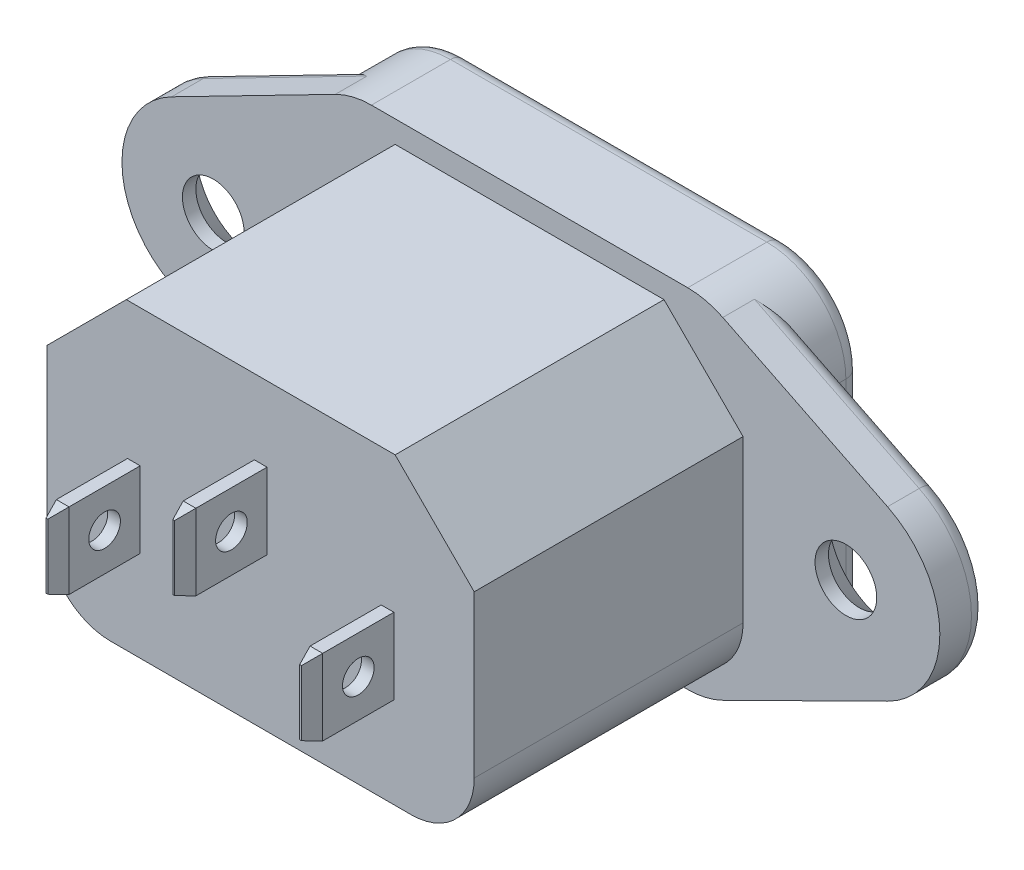
SolidWorks part; units mm, degrees
ref_plane "Front Plane" through (0, 0, 0) normal (0, 0, 1) x (1, 0, 0)
ref_plane "Top Plane" through (0, 0, 0) normal (0, 1, 0) x (1, 0, 0)
ref_plane "Right Plane" through (0, 0, 0) normal (1, 0, 0) x (0, 0, -1)
sketch "Sketch1" plane through (0, 0, 0) normal (0, 0, 1) x (1, 0, 0)
  line L0 (0, 14.2) -> (-5, 19.2)
  line L1 (-4, 0) -> (-23, 0)
  line L2 (0, 4) -> (0, 14.2)
  line L3 (-5, 19.2) -> (-22, 19.2)
  line L4 (-27, 4) -> (-27, 14.2)
  line L5 (-27, 14.2) -> (-22, 19.2)
  arc A0 (-4, 0) -> (0, 4) centre (-4, 4) ccw
  arc A1 (-27, 4) -> (-23, 0) centre (-23, 4) ccw
  point P1 (-27, 19.2)
  point P2 (0, 19.2)
  point P7 (0, 0)
  dimension "D3" = 4
  dimension "D4" = 4
  dimension "D1" = 19.2
  dimension "D2" = 27
extrude "Boss-Extrude1" add sketch "Sketch1" along normal blind 17
sketch "Sketch7" plane through (0, 0, 0) normal (0, 0, 1) x (1, 0, 0)
  line L0 (-13.5, 19.2) -> (-13.5, 0) construction
  line L1 (1.5, -1.4) -> (-28.5, -1.4)
  line L2 (1.5, -1.4) -> (1.5, 20.6)
  line L3 (1.5, 20.6) -> (-28.5, 20.6)
  line L4 (-28.5, -1.4) -> (-28.5, 20.6)
  line L5 (-5, 19.2) -> (-22, 19.2) construction
  line L6 (-23, 0) -> (-4, 0) construction
  line L7 (0, 9.6) -> (-27, 9.6) construction
  line L8 (0, 4) -> (0, 14.2) construction
  line L9 (-27, 14.2) -> (-27, 4) construction
  dimension "D1" = 22
  dimension "D2" = 30
extrude "Boss-Extrude5" add sketch "Sketch7" against normal blind 6
fillet "Fillet13" radius 5 4 edges at (1.5, -1.4, -3) (-28.5, -1.4, -3) (-28.5, 20.6, -3) (1.5, 20.6, -3)
sketch "Sketch8" plane through (0, 0, 0) normal (0, 0, 1) x (1, 0, 0)
  line L0 (-13.5, 31.1212) -> (-13.5, -11.3132) construction
  line L1 (-6.5, 17.6) -> (-20.5, 17.6)
  line L2 (-1.5, 12.6) -> (-1.5, 3.6)
  line L3 (-3.5, 1.6) -> (-23.5, 1.6)
  line L4 (-25.5, 12.6) -> (-25.5, 3.6)
  line L5 (-20.5, 17.6) -> (-25.5, 12.6)
  line L7 (20.2859, 9.6) -> (-48.0141, 9.6) construction
  line L8 (1.5, 3.6) -> (1.5, 15.6) construction
  line L9 (-28.5, 15.6) -> (-28.5, 3.6) construction
  line L10 (-5, 19.2) -> (-22, 19.2) construction
  line L11 (-23, 0) -> (-4, 0) construction
  line L12 (-6.5, 17.6) -> (-1.5, 12.6)
  arc A0 (-3.5, 1.6) -> (-1.5, 3.6) centre (-3.5, 3.6) ccw
  arc A1 (-25.5, 3.6) -> (-23.5, 1.6) centre (-23.5, 3.6) ccw
  point P0 (-1.5, 17.6)
  point P3 (-25.5, 17.6)
  point P20 (-25.5, 1.6)
  dimension "D3" = 2
  dimension "D4" = 2
  dimension "D1" = 24
  dimension "D2" = 16
  dimension "D5" = 5
  dimension "D6" = 5
extrude "Cut-Extrude1" cut sketch "Sketch8" along normal blind 16 and the other way blind 6
sketch "Sketch9" plane through (0, 0, 0) normal (0, 0, 1) x (1, 0, 0)
  line L0 (-13.5, 32.7328) -> (-13.5, -17.166) construction
  line L1 (-36.1355, 4.463) -> (-25.7824, -0.8487)
  line L2 (-36.1355, 14.737) -> (-25.7824, 20.0487)
  line L3 (50.8382, 9.6) -> (-68.6144, 9.6) construction
  line L4 (-3.5, 20.6) -> (-23.5, 20.6) construction
  line L5 (9.1356, 14.9256) -> (-1.2823, 20.0813)
  line L6 (9.1356, 4.2744) -> (-1.2823, -0.8813)
  line L7 (-23.5, -1.4) -> (-3.5, -1.4) construction
  line L8 (-1.2823, 20.0813) -> (-1.2823, -0.8813)
  line L9 (-1.2823, -0.8813) -> (-1.5852, -0.8164)
  line L10 (-25.7824, 20.0487) -> (-25.7824, -0.8487)
  line L11 (1.5, 3.6) -> (1.5, 15.6) construction
  line L12 (-28.5, 15.6) -> (-28.5, 3.6) construction
  arc A0 (9.1356, 4.2744) -> (9.1356, 14.9256) centre (6.5, 9.6) ccw
  arc A1 (1.5, 15.6) -> (-3.5, 20.6) centre (-3.5, 15.6) ccw construction
  arc A2 (-3.5, -1.4) -> (1.5, 3.6) centre (-3.5, 3.6) ccw construction
  arc A3 (-36.1355, 14.737) -> (-36.1355, 4.463) centre (-33.5, 9.6) ccw
  arc A4 (-28.5, 3.6) -> (-23.5, -1.4) centre (-23.5, 3.6) ccw construction
  arc A5 (-23.5, 20.6) -> (-28.5, 15.6) centre (-23.5, 15.6) ccw construction
  point P0 (6.5, 9.6)
  point P1 (-33.5, 9.6)
  dimension "D1" = 40
extrude "Boss-Extrude6" add sketch "Sketch9" against normal blind 3 contours L6 A0 L5 L8 | L2 A3 L1 L10
hole_wizard "CSK for M3.5 Flat Head Machine Screw1" positions "Sketch11" profile "Sketch10" countersink size "M3.5" standard "ANSI Metric" end condition up to next
sketch "Sketch11" plane through (0, 0, -3) normal (0, 0, -1) x (-1, 0, 0)
  line L0 (13.5, 27.5168) -> (13.5, -20.2429) construction
  line L1 (-16.2874, 9.6) -> (52.2441, 9.6) construction
  line L2 (3.5, 20.6) -> (23.5, 20.6) construction
  line L3 (23.5, -1.4) -> (3.5, -1.4) construction
  line L4 (28.5, 15.6) -> (28.5, 3.6) construction
  line L5 (-1.5, 15.6) -> (-1.5, 3.6) construction
  point P0 (-6.5, 9.6)
  point P2 (33.5, 9.6)
  dimension "D1" = 40
sketch "Sketch10" plane through (6.5, 9.6, -3) normal (1, 0, 0) x (0, 1, 0)
  line L0 (0, 0) -> (0, 3)
  line L1 (0, 3) -> (1.95, 3)
  line L2 (1.95, 3) -> (1.95, 2.15)
  line L3 (1.95, 2.15) -> (4.1, 0)
  line L5 (4.1, 0) -> (0, 0)
  line L6 (-1.95, 2.15) -> (-4.1, 0) construction
  line L11 (0, -6.35) -> (0, 107.95) construction
  dimension "Thru Hole Dia." = 3.9
  dimension "Thru Hole Depth" = 3
  dimension "Near C'Sink Dia." = 8.2
  dimension "Near C'Sink Angle" = 90
sketch "Sketch12" plane through (0, 0, 16) normal (0, 0, -1) x (-1, 0, 0)
  line L0 (1.5, 5.6) -> (25.5, 5.6) construction
  line L1 (4.21, 10.68) -> (6.75, 10.68)
  line L2 (4.21, 10.68) -> (4.21, 5.6)
  line L3 (4.21, 5.6) -> (6.75, 5.6)
  line L4 (6.75, 10.68) -> (6.75, 5.6)
  line L5 (20.25, 10.68) -> (22.79, 10.68)
  line L6 (20.25, 10.68) -> (20.25, 5.6)
  line L7 (20.25, 5.6) -> (22.79, 5.6)
  line L8 (22.79, 10.68) -> (22.79, 5.6)
  line L9 (12.23, 14.6159) -> (14.77, 14.6159)
  line L10 (12.23, 14.6159) -> (12.23, 9.5359)
  line L11 (12.23, 9.5359) -> (14.77, 9.5359)
  line L12 (14.77, 14.6159) -> (14.77, 9.5359)
  line L13 (1.5, 3.6) -> (1.5, 12.6) construction
  line L14 (25.5, 12.6) -> (25.5, 3.6) construction
  line L15 (13.5, 17.6) -> (13.5, 1.6) construction
  line L16 (6.5, 17.6) -> (20.5, 17.6) construction
  line L17 (23.5, 1.6) -> (3.5, 1.6) construction
  line L18 (23.5, -1.4) -> (3.5, -1.4) construction
  dimension "D1" = 2.54
  dimension "D2" = 5.08
  dimension "D3" = 13.5
  dimension "D4" = 7
  dimension "D5" = 10.9359
extrude "Boss-Extrude7" add sketch "Sketch12" along normal blind 15 and the other way blind 5.5
sketch "Sketch13" plane through (0, 0, 1) normal (0, 0, -1) x (-1, 0, 0)
  line L0 (6.75, 10.68) -> (4.21, 10.68) construction
  line L1 (4.21, 10.68) -> (6.75, 10.68)
  line L2 (4.21, 10.68) -> (4.21, 5.6)
  line L3 (4.21, 5.6) -> (6.75, 5.6)
  line L4 (6.75, 10.68) -> (6.75, 5.6)
  line L5 (4.21, 10.68) -> (4.21, 5.6) construction
  line L6 (14.77, 9.5359) -> (14.77, 14.6159) construction
  line L7 (12.23, 14.6159) -> (14.77, 14.6159)
  line L8 (12.23, 14.6159) -> (12.23, 9.5359)
  line L9 (12.23, 9.5359) -> (14.77, 9.5359)
  line L10 (14.77, 14.6159) -> (14.77, 9.5359)
  line L12 (20.25, 10.68) -> (22.79, 10.68)
  line L13 (20.25, 10.68) -> (20.25, 5.6)
  line L14 (20.25, 5.6) -> (22.79, 5.6)
  line L15 (22.79, 10.68) -> (22.79, 5.6)
extrude "Boss-Extrude8" add sketch "Sketch13" along normal blind 2 draft 28
sketch "Sketch14" plane through (0, 0, 21.5) normal (0, 0, 1) x (1, 0, 0)
  line L1 (-21.92, 10.54) -> (-21.12, 10.54)
  line L2 (-21.92, 10.54) -> (-21.92, 5.74)
  line L3 (-21.92, 5.74) -> (-21.12, 5.74)
  line L4 (-21.12, 10.54) -> (-21.12, 5.74)
  line L5 (-13.9, 14.4759) -> (-13.1, 14.4759)
  line L6 (-13.9, 14.4759) -> (-13.9, 9.6759)
  line L7 (-13.9, 9.6759) -> (-13.1, 9.6759)
  line L8 (-13.1, 14.4759) -> (-13.1, 9.6759)
  line L9 (-5.88, 10.54) -> (-5.08, 10.54)
  line L10 (-5.88, 10.54) -> (-5.88, 5.74)
  line L11 (-5.88, 5.74) -> (-5.08, 5.74)
  line L12 (-5.08, 10.54) -> (-5.08, 5.74)
  line L15 (-21.52, 10.68) -> (-21.52, 5.6) construction
  line L16 (-22.79, 10.68) -> (-20.25, 10.68) construction
  line L17 (-20.25, 5.6) -> (-22.79, 5.6) construction
  line L18 (-22.79, 8.14) -> (-20.25, 8.14) construction
  line L19 (-22.79, 5.6) -> (-22.79, 10.68) construction
  line L20 (-20.25, 10.68) -> (-20.25, 5.6) construction
  line L21 (-13.5, 14.6159) -> (-13.5, 9.5359) construction
  line L22 (-14.77, 14.6159) -> (-12.23, 14.6159) construction
  line L23 (-12.23, 9.5359) -> (-14.77, 9.5359) construction
  line L24 (-14.77, 12.0759) -> (-12.23, 12.0759) construction
  line L25 (-14.77, 9.5359) -> (-14.77, 14.6159) construction
  line L26 (-12.23, 14.6159) -> (-12.23, 9.5359) construction
  line L27 (-6.75, 8.14) -> (-4.21, 8.14) construction
  line L28 (-6.75, 5.6) -> (-6.75, 10.68) construction
  line L29 (-4.21, 10.68) -> (-4.21, 5.6) construction
  line L30 (-5.48, 5.6) -> (-5.48, 10.68) construction
  line L31 (-4.21, 5.6) -> (-6.75, 5.6) construction
  line L32 (-6.75, 10.68) -> (-4.21, 10.68) construction
  dimension "D1" = 0.8
  dimension "D2" = 4.8
extrude "Cut-Extrude2" cut sketch "Sketch14" against normal up to surface (4.5 mm away) flip side to cut up to face at (-13.5, 12.0759, 17)
hole_wizard "Ø2.0mm Dowel Hole1" positions "Sketch16" profile "Sketch15" hole size "Ø2.0" standard "ANSI Metric" end condition through all
sketch "Sketch16" plane through (-21.92, 0, 0) normal (-1, 0, 0) x (0, 0, 1)
  line L2 (17, 8.14) -> (21.5, 8.14) construction
  line L3 (17, 5.74) -> (17, 10.54) construction
  line L4 (21.5, 10.54) -> (21.5, 5.74) construction
  line L6 (19.25, 5.6) -> (19.25, 10.68) construction
  line L7 (21.5, 5.6) -> (17, 5.6) construction
  line L8 (17, 10.68) -> (21.5, 10.68) construction
  point P0 (19.25, 8.14)
sketch "Sketch15" plane through (-21.92, 8.14, 19.25) normal (0, 1, 0) x (0, 0, 1)
  line L0 (0, 0) -> (0, 34.3621)
  line L1 (0, 34.3621) -> (1, 34.3621)
  line L2 (1, 34.3621) -> (1, 0)
  line L5 (1, 0) -> (0, 0)
  line L11 (0, -6.35) -> (0, 107.95) construction
  dimension "Thru Hole Dia." = 2
  dimension "Thru Hole Depth" = 34.3621
hole_wizard "Ø2.0mm Dowel Hole2" positions "Sketch18" profile "Sketch17" hole size "Ø2.0" standard "ANSI Metric"
sketch "Sketch18" plane through (-13.9, 0, 0) normal (-1, 0, 0) x (0, 0, 1)
  line L0 (19.25, 14.6159) -> (19.25, 9.5359) construction
  line L1 (17, 14.6159) -> (21.5, 14.6159) construction
  line L2 (21.5, 9.5359) -> (17, 9.5359) construction
  line L4 (17, 12.0759) -> (21.5, 12.0759) construction
  line L5 (17, 9.6759) -> (17, 14.4759) construction
  line L6 (21.5, 9.6759) -> (21.5, 14.4759) construction
  point P0 (19.25, 12.0759)
sketch "Sketch17" plane through (-13.9, 12.0759, 19.25) normal (0, 1, 0) x (0, 0, 1)
  line L0 (0, 0) -> (0, 3.1409)
  line L1 (0, 3.1409) -> (1, 2.54)
  line L2 (1, 2.54) -> (1, 0)
  line L5 (1, 0) -> (0, 0)
  line L10 (0, 3.1409) -> (-1, 2.54) construction
  line L11 (0, -6.35) -> (0, 107.95) construction
  dimension "Hole Dia." = 2
  dimension "Hole Depth" = 2.54
  dimension "Drill Angle" = 118
sketch "Sketch20" plane through (0, 0, 21.5) normal (0, 0, 1) x (1, 0, 0)
  line L1 (-21.92, 10.54) -> (-21.12, 10.54)
  line L2 (-21.92, 10.54) -> (-21.92, 5.74)
  line L3 (-21.92, 5.74) -> (-21.12, 5.74)
  line L4 (-21.12, 10.54) -> (-21.12, 5.74)
  line L5 (-13.9, 14.4759) -> (-13.1, 14.4759)
  line L6 (-13.9, 14.4759) -> (-13.9, 9.6759)
  line L7 (-13.9, 9.6759) -> (-13.1, 9.6759)
  line L8 (-13.1, 14.4759) -> (-13.1, 9.6759)
  line L9 (-5.88, 10.54) -> (-5.08, 10.54)
  line L10 (-5.88, 10.54) -> (-5.88, 5.74)
  line L11 (-5.88, 5.74) -> (-5.08, 5.74)
  line L12 (-5.08, 10.54) -> (-5.08, 5.74)
extrude "Boss-Extrude10" add sketch "Sketch20" along normal blind 1 draft 19
fillet "Fillet14" radius 1 3 edges at (3.9266, 17.5034, -3) (12.4421, 9.6, -3) (3.9266, 1.6966, -3)
fillet "Fillet15" radius 1 3 edges at (-30.959, 1.8072, -3) (-39.2736, 9.6, -3) (-30.959, 17.3928, -3)
fillet "Fillet16" radius 1 8 edges at (-13.5, -1.4, -6) (1.5, 9.6, -6) (-28.5, 9.6, -6) (-13.5, 20.6, -6) (0.0355, 19.1355, -6) (-27.0355, 19.1355, -6) (-27.0355, 0.0645, -6) (0.0355, 0.0645, -6)
